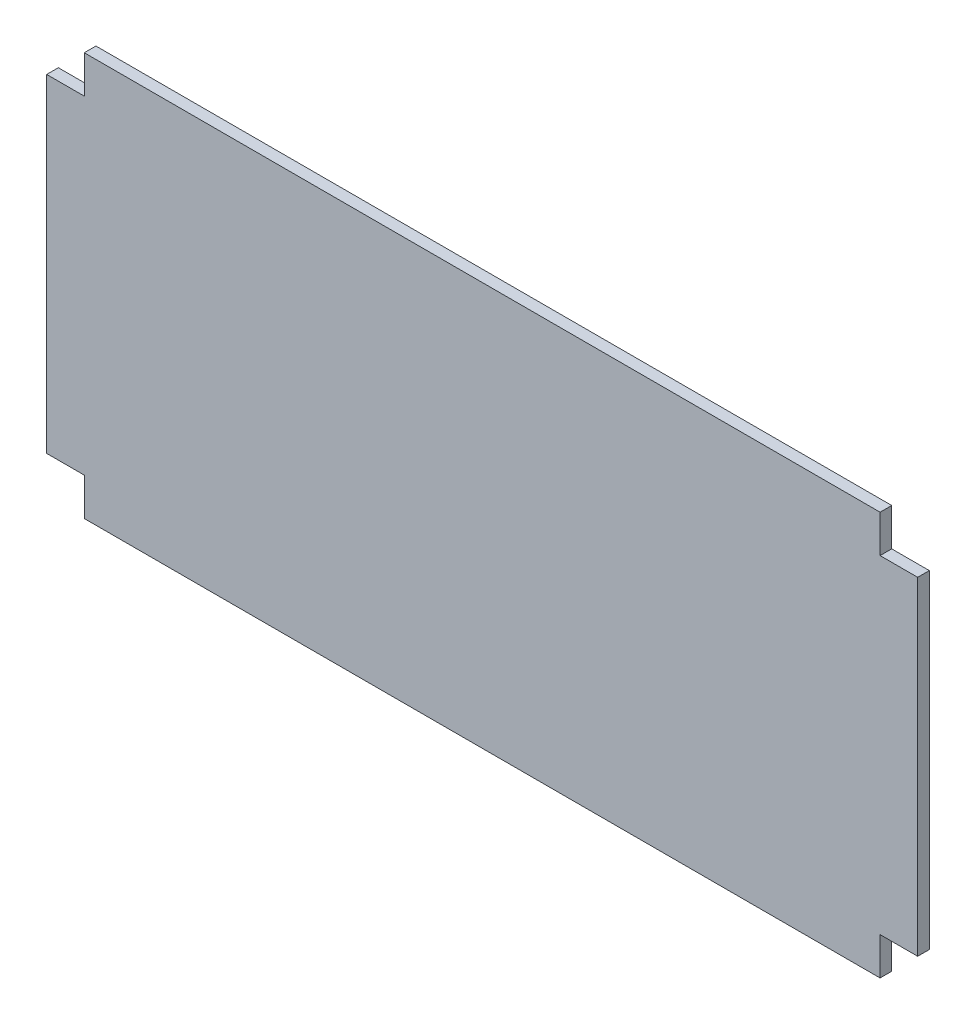
SolidWorks part; units mm, degrees
ref_plane "Front Plane" through (0, 0, 0) normal (0, 0, 1) x (1, 0, 0)
ref_plane "Top Plane" through (0, 0, 0) normal (0, 1, 0) x (1, 0, 0)
ref_plane "Right Plane" through (0, 0, 0) normal (1, 0, 0) x (0, 0, -1)
sketch "Sketch2" plane through (0, 0, 0) normal (0, 0, 1) x (1, 0, 0)
  line L1 (-475, -220) -> (475, -220)
  line L2 (-475, -220) -> (-475, 220)
  line L3 (-475, 220) -> (475, 220)
  line L4 (475, -220) -> (475, 220)
  line L5 (-475, -220) -> (475, 220) construction
  line L6 (-475, 220) -> (475, -220) construction
  point P0 (0, 0)
  dimension "D1" = 950
  dimension "D2" = 440
extrude "Boss-Extrude1" add sketch "Sketch2" along normal blind 12.7
sketch "Sketch3" plane through (0, 0, 12.7) normal (0, 0, 1) x (1, 0, 0)
  line L0 (0, 220) -> (0, -220) construction
  line L1 (-475, 220) -> (-434, 220)
  line L2 (-475, 220) -> (-475, 179)
  line L3 (-475, 179) -> (-434, 179)
  line L4 (-434, 220) -> (-434, 179)
  line L5 (-475, 220) -> (-434, 179) construction
  line L6 (-475, 179) -> (-434, 220) construction
  line L7 (475, 220) -> (-475, 220) construction
  line L8 (-475, -220) -> (475, -220) construction
  line L9 (-475, 0) -> (475, 0) construction
  line L10 (-475, 220) -> (-475, -220) construction
  line L11 (475, -220) -> (475, 220) construction
  line L12 (475, 179) -> (434, 220) construction
  line L13 (475, 220) -> (434, 179) construction
  line L14 (434, 220) -> (434, 179)
  line L15 (475, 179) -> (434, 179)
  line L16 (475, 220) -> (475, 179)
  line L17 (475, 220) -> (434, 220)
  line L18 (475, -220) -> (434, -179) construction
  line L19 (475, -179) -> (434, -220) construction
  line L20 (475, -220) -> (434, -220)
  line L21 (475, -220) -> (475, -179)
  line L22 (434, -220) -> (434, -179)
  line L23 (475, -179) -> (434, -179)
  line L24 (-475, -179) -> (-434, -220) construction
  line L25 (-475, -220) -> (-434, -179) construction
  line L26 (-434, -220) -> (-434, -179)
  line L27 (-475, -179) -> (-434, -179)
  line L28 (-475, -220) -> (-475, -179)
  line L29 (-475, -220) -> (-434, -220)
  point P4 (-454.5, 199.5)
  point P22 (454.5, 199.5)
  point P27 (454.5, -199.5)
  point P32 (-454.5, -199.5)
  dimension "D1" = 41
  dimension "D2" = 41
extrude "Cut-Extrude1" cut sketch "Sketch3" against normal up to next
